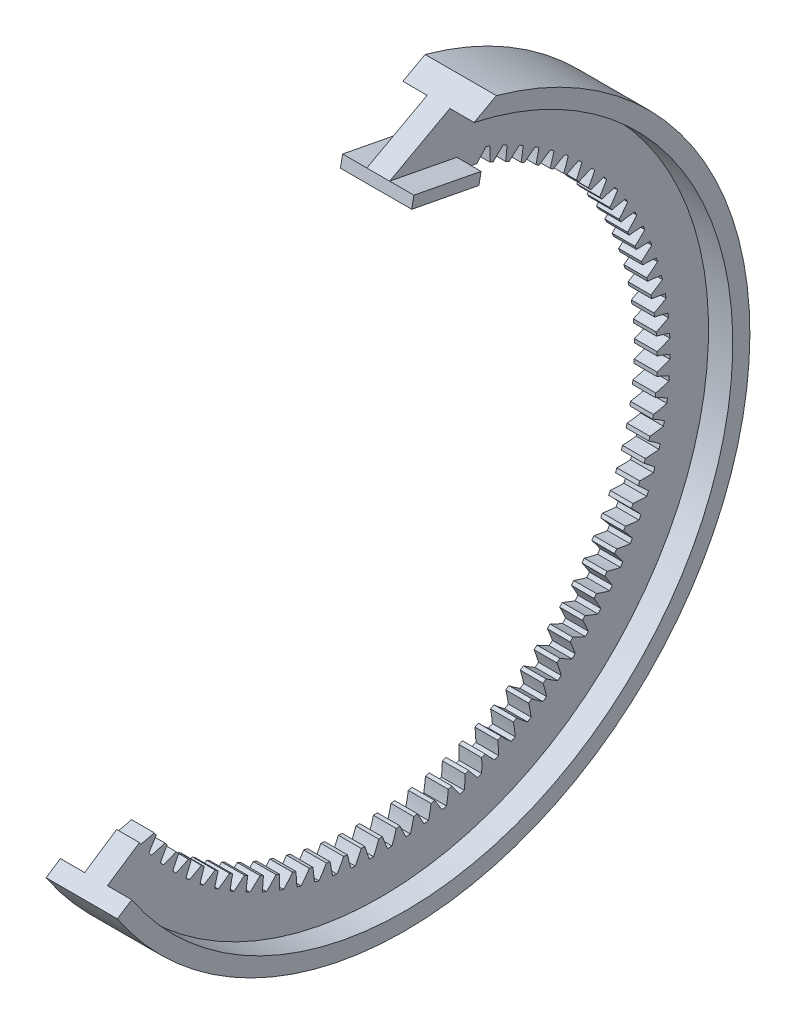
SolidWorks part; units mm, degrees
ref_plane "Plane1" through (0, 0, 0) normal (0, 0, 1) x (1, 0, 0)
ref_plane "Plane2" through (0, 0, 0) normal (0, 1, 0) x (1, 0, 0)
ref_plane "Plane3" through (0, 0, 0) normal (1, 0, 0) x (0, 0, -1)
other "Configuration Table"
sketch "HoldingSke" plane through (0, 0, 0) normal (0, 1, 0) x (1, 0, 0)
  line L0 (0, 0) -> (-0.0262, -0.4993)
  line L1 (-15, 0) -> (100, 0) construction
  line L2 (0, 0) -> (-2.1039, 2.3779)
  line L3 (0, 0) -> (-11.863, 4.5341)
  line L4 (0, 0) -> (-1.351, 8.5297)
  line L5 (0, 0) -> (-23.7986, -8.8762)
  line L6 (0, 0) -> (-10.5278, -7.1032)
  line L7 (-2.1039, 2.3779) -> (3.3635, 27.1825)
  line L8 (-76.2, 4.3779) -> (-54.61, 4.3779)
  line L9 (-71.009, 38.7566) -> (-53.1078, 45.2721)
  line L10 (-76.2, 71.12) -> (104.1128, 71.12)
  line L11 (0, 0) -> (-8, 0)
  line L12 (-76.2, 101.6) -> (-76.133, 101.6)
  line L13 (24.9733, 27.94) -> (52.9518, 28.4284)
  line L14 (24.9733, 27.94) -> (24.9743, 27.94)
  line L15 (24.9733, 27.94) -> (100.4006, 29.5858)
  circle A0 centre (0, 0) radius 105
  circle A1 centre (0, 0) radius 12.7
  circle A2 centre (0, 0) radius 12.7
  dimension "MHD" = 25.4
  dimension "Hub_dia" = 25.4
  dimension "Diameter" = 210
  dimension "Num_teeth" = 99
  dimension "Pitch" = 0.5
  dimension "Overall_len" = 25.4
  dimension "Show_teeth" = 93
  dimension "Thickness" = 12.7
  dimension "OAL" = 25.4001
  dimension "T_dim" = 21.59
  dimension "Ap" = 20
  dimension "H" = 19.05
  dimension "Pitch_radius" = 180.3128
  dimension "Width" = 8
  dimension "Backlash" = 0.067
  dimension "Addendum_fac" = 1
  dimension "Dedendum_fac" = 1.25
  dimension "Clearance_fac" = 0.25
  dimension "Dedendum_add" = 0.001
  dimension "Module" = 2
ref_axis "Assi1" through (0, 0, 0) along (0, 1, 0)
sketch "BasProSke" plane through (0, 0, 0) normal (0, 1, 0) x (1, 0, 0)
  line L0 (-10, 0) -> (60, 0) construction
  line L1 (0, 97) -> (0, 105)
  line L2 (0, 97) -> (8, 97)
  line L3 (8, 97) -> (8, 105)
  line L4 (8, 105) -> (0, 105)
  dimension "Diameter" = 210
  dimension "Thickness" = 8
  dimension "Inside_diameter" = 194
revolve "Base-Revolve" add sketch "BasProSke" angle 360 about L0
sketch "TooCutSke" plane through (0, 0, 0) normal (1, 0, 0) x (0, 0, -1)
  line L3 (1.7382, 98.9847) -> (1.7382, 53.6633) construction
  line L4 (0, 0) -> (0, 59.563) construction
  line L5 (0, 0) -> (-2.1679, 68.2931) construction
  line L6 (-44.8809, 82.3441) -> (35.1673, 84.8851) construction
  circle A0 centre (0, 0) radius 99 construction
  circle A1 centre (0, 0) radius 101.501 construction
  circle A2 centre (0, 0) radius 83.7266 construction
  circle A3 centre (0, 0) radius 96.9746 construction
  arc A4 (2.4169, 96.9445) -> (0.7631, 101.4981) centre (-44.8809, 82.3441) ccw
  arc A5 (2.4169, 96.9445) -> (-2.4169, 96.9445) centre (0, 0) ccw
  arc A6 (0.7631, 101.4981) -> (-0.7631, 101.4981) centre (0, 0) ccw
  arc A7 (-0.7631, 101.4981) -> (-2.4169, 96.9445) centre (44.8809, 82.3441) ccw
  dimension "Pitch_dia" = 198
  dimension "Base_dia" = 167.4532
  dimension "Root_dia" = 203.002
  dimension "Overcut_dia" = 193.9492
  dimension "Flank_rad" = 49.5
  dimension "Half_ang" = 1.818
  dimension "Half_CT" = 1.7382
extrude "ToothCut" cut sketch "TooCutSke" along normal through all
fillet "Breaks" [suppressed] radius 0.2
fillet "RootFillets" [suppressed] radius 0.501
pattern_circular "TeethCuts" count 94 every 3.636 about axis through (-10, 0, 0) along (1, 0, 0) of "RootFillets", "Breaks", "ToothCut"
sketch "Schizzo1" plane through (8, 0, 0) normal (1, 0, 0) x (0, 0, -1)
  line L0 (18.3574, 95.2471) -> (0, 0) construction
  line L1 (0, 0) -> (-87.4801, -58.0709)
  line L2 (18.3574, 95.2471) -> (19.8714, 103.1025) construction
  line L3 (0, 0) -> (2.409, 96.9701)
  line L4 (2.409, 96.9701) -> (2.6077, 104.9676)
  line L5 (0, 0) -> (76.0672, 72.3794) construction
  arc A0 (33.8037, 90.9193) -> (2.409, 96.9701) centre (0, 0) ccw construction
  circle A1 centre (0, 0) radius 105 construction
  arc A2 (2.6077, 104.9676) -> (-87.4801, -58.0709) centre (0, 0) ccw
  dimension "D1" = 125
  dimension "D2" = 45
extrude "Taglio-Estrusione1" cut sketch "Schizzo1" against normal blind 10
sketch "Schizzo2" plane through (8, 0, 0) normal (1, 0, 0) x (0, 0, -1)
  line L2 (2.409, 96.9701) -> (33.8037, 90.9193)
  arc A0 (33.8037, 90.9193) -> (2.409, 96.9701) centre (0, 0) ccw
extrude "Estrusione-Estrusione1" add sketch "Schizzo2" against normal blind 8
sketch "Schizzo3" plane through (0, 93.9447, -18.1064) normal (0, -0.9819, 0.1893) x (1, 0, 0)
  line L0 (0, 15.9862) -> (8, 15.9862) construction
  line L1 (-8.5, -8.0138) -> (16.5, -8.0138)
  line L2 (-8.5, -8.0138) -> (-8.5, 15.9862)
  line L3 (-8.5, 15.9862) -> (16.5, 15.9862)
  line L4 (16.5, -8.0138) -> (16.5, 15.9862)
  line L5 (0, 15.9862) -> (0, -8.0138)
  line L6 (0, 15.9862) -> (0, -15.9862) construction
  line L7 (8, 15.9862) -> (8, -8.0138)
  line L8 (8, 15.9862) -> (8, -15.9862) construction
  point P6 (4, 15.9862)
  point P7 (4, 15.9862)
  line M5 (8, -15.9862) -> (8, 15.9862)
  line M7 (0, 15.9862) -> (0, -15.9862)
  dimension "D1" = 25
  dimension "D2" = 24
extrude "Estrusione-Estrusione2" add sketch "Schizzo3" against normal blind 4 contours L3 L2 L1 M7 | L1 L4 L3 M5 region at (-4.25, 94.6991, -14.1921) region at (12.25, 94.6991, -14.1921)
sketch "Schizzo4" plane through (0, 0, 0) normal (0, 0.0248, 0.9997) x (1, 0, 0)
  line L0 (0, 105) -> (0, 115)
  line L1 (0, 115) -> (-8.5, 115)
  line L2 (-8.5, 115) -> (-8.5, 121)
  line L3 (-8.5, 121) -> (16.5, 121)
  line L4 (16.5, 121) -> (16.5, 115)
  line L5 (16.5, 115) -> (8, 115)
  line L6 (8, 115) -> (8, 105)
  line L9 (4, 121) -> (4, 105) construction
  line L10 (0, 105) -> (8, 105) construction
  line L11 (0, 105) -> (8, 105)
  line L12 (-101.9075, 0) -> (149.4298, 0) construction
  dimension "D1" = 10
  dimension "D2" = 6
  dimension "D3" = 25
revolve "Rivoluzione1" add sketch "Schizzo4" angle 235 about L12 reverse direction yes
sketch "Schizzo5" plane through (16.5, 0, 0) normal (1, 0, 0) x (0, 0, -1)
  line L0 (3.166, 100.8978) -> (32.1079, 116.6623)
  line L1 (3.166, 100.8978) -> (2.409, 96.9701)
  line L2 (2.409, 96.9701) -> (3.005, 120.9627)
  arc A1 (-100.8104, -66.9198) -> (3.005, 120.9627) centre (0, 0) ccw construction
  arc A2 (32.1079, 116.6623) -> (3.005, 120.9627) centre (0, 0) ccw
  dimension "D1" = 60
extrude "Taglio-Estrusione2" cut sketch "Schizzo5" against normal blind 25
equation "' \"Module@HoldingSke\" = 6.35"
equation "' \"Num_teeth@HoldingSke\" = 24"
equation "' \"Ap@HoldingSke\" =  14.5"
equation "' \"Ap@HoldingSke\" = 14.5"
equation "' \"Width@HoldingSke\" = 12"
equation "' \"Diameter@HoldingSke\" = 8 * 25.4"
equation "' \"Show_teeth@HoldingSke\" = 100"
equation "' \"Backlash@HoldingSke\" = 0.009 * 25.4"
equation "' \"Addendum_fac@HoldingSke\" = 1.0"
equation "' \"Dedendum_fac@HoldingSke\" = 1.25"
equation "' \"Dedendum_add@HoldingSke\" = 0.00005 * 25.4"
equation "' \"Clearance_fac@HoldingSke\" = 0.25"
equation "\"Pitch@HoldingSke\" = 1 / \"Module@HoldingSke\" "
equation "\"Overcut_dia@TooCutSke\" = (\"Num_teeth@HoldingSke\" - 2 * \"Addendum_fac@HoldingSke\") / \"Pitch@HoldingSke\" - 0.002 * 25.4"
equation "\"Pitch_dia@TooCutSke\" = \"Num_teeth@HoldingSke\" / \"Pitch@HoldingSke\""
equation "\"Base_dia@TooCutSke\" = \"Num_teeth@HoldingSke\" / \"Pitch@HoldingSke\" * cos((\"Ap@HoldingSke\"  * 3.14159265 / 180)) * 0.90"
equation "\"Root_dia@TooCutSke\" = \"Num_teeth@HoldingSke\"  / \"Pitch@HoldingSke\" + 2 *  \"Dedendum_fac@HoldingSke\"/ \"Pitch@HoldingSke\" + \"Dedendum_add@HoldingSke\" * 2"
equation "\"Half_ang@TooCutSke\" = 180 / \"Num_teeth@HoldingSke\""
equation "\"Half_CT@TooCutSke\" = \"Num_teeth@HoldingSke\" / \"Pitch@HoldingSke\" * sin((3.14159265 / 2 / \"Num_teeth@HoldingSke\")) / 2 + 10 * \"Backlash@HoldingSke\" / 4"
equation "\"Flank_rad@TooCutSke\" = \"Num_teeth@HoldingSke\" / \"Pitch@HoldingSke\" / 4"
equation "\"Radius@RootFillets\"= \"Clearance_fac@HoldingSke\" / \"Pitch@HoldingSke\" + \"Dedendum_add@HoldingSke\""
equation "\"Break_rad@Breaks\" = 0.02 / \"Pitch@HoldingSke\" * 5"
equation "\"Num_teeth@TeethCuts\" = int( \"Show_teeth@HoldingSke\" ) + 1"
equation "\"Num_teeth@TeethCuts\" = ((sgn( \"Num_teeth@TeethCuts\" - \"Num_teeth@HoldingSke\" )-1)*( \"Num_teeth@TeethCuts\" - \"Num_teeth@HoldingSke\" ))/-2+ \"Num_teeth@HoldingSke\""
equation "\"Num_teeth@TeethCuts\" = ((sgn( \"Num_teeth@TeethCuts\" - 2.0)+1)*( \"Num_teeth@TeethCuts\" - 2.0))/2 +2.0"
equation "\"Angle@TeethCuts\" = 360.0 / \"Num_teeth@HoldingSke\""
equation "\"Diameter@BasProSke\" = \"Num_teeth@HoldingSke\"  / \"Pitch@HoldingSke\" + 2 *  \"Dedendum_fac@HoldingSke\"/ \"Pitch@HoldingSke\" + \"Dedendum_add@HoldingSke\" * 2 + 0.002 * 25.4"
equation "\"Diameter@BasProSke\" = ((sgn( \"Diameter@BasProSke\"  - \"Diameter@HoldingSke\" )+1)*( \"Diameter@BasProSke\"  - \"Diameter@HoldingSke\" ))/2 + \"Diameter@HoldingSke\""
equation "\"Inside_diameter@BasProSke\" =  (\"Num_teeth@HoldingSke\" - 2 * \"Addendum_fac@HoldingSke\") / \"Pitch@HoldingSke\" "
equation "\"Thickness@BasProSke\"  = \"Width@HoldingSke\""
